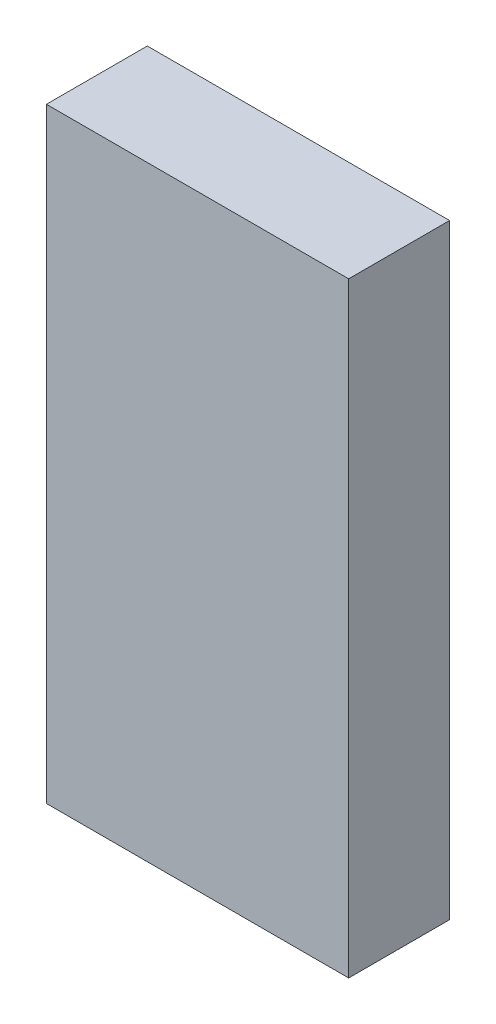
SolidWorks part; units mm, degrees
material "Polyurethane Foam Rigid"
ref_plane "X-Y Datum" through (0, 0, 0) normal (0, 0, 1) x (1, 0, 0)
ref_plane "X-Z Datum" through (0, 0, 0) normal (0, 1, 0) x (1, 0, 0)
ref_plane "Y-Z Datum" through (0, 0, 0) normal (1, 0, 0) x (0, 0, -1)
sketch "Sketch1" plane through (0, 0, 0) normal (0, 0, 1) x (1, 0, 0)
  line L1 (-38.0378, -76.2) -> (38.0378, -76.2)
  line L2 (-38.0378, -76.2) -> (-38.0378, 76.2)
  line L3 (-38.0378, 76.2) -> (38.0378, 76.2)
  line L4 (38.0378, -76.2) -> (38.0378, 76.2)
  line L5 (-38.0378, -76.2) -> (38.0378, 76.2) construction
  line L6 (-38.0378, 76.2) -> (38.0378, -76.2) construction
  point P0 (0, 0)
  dimension "D1" = 76.0755
  dimension "D2" = 152.4
extrude "Boss-Extrude1" add sketch "Sketch1" along normal blind 25.4
